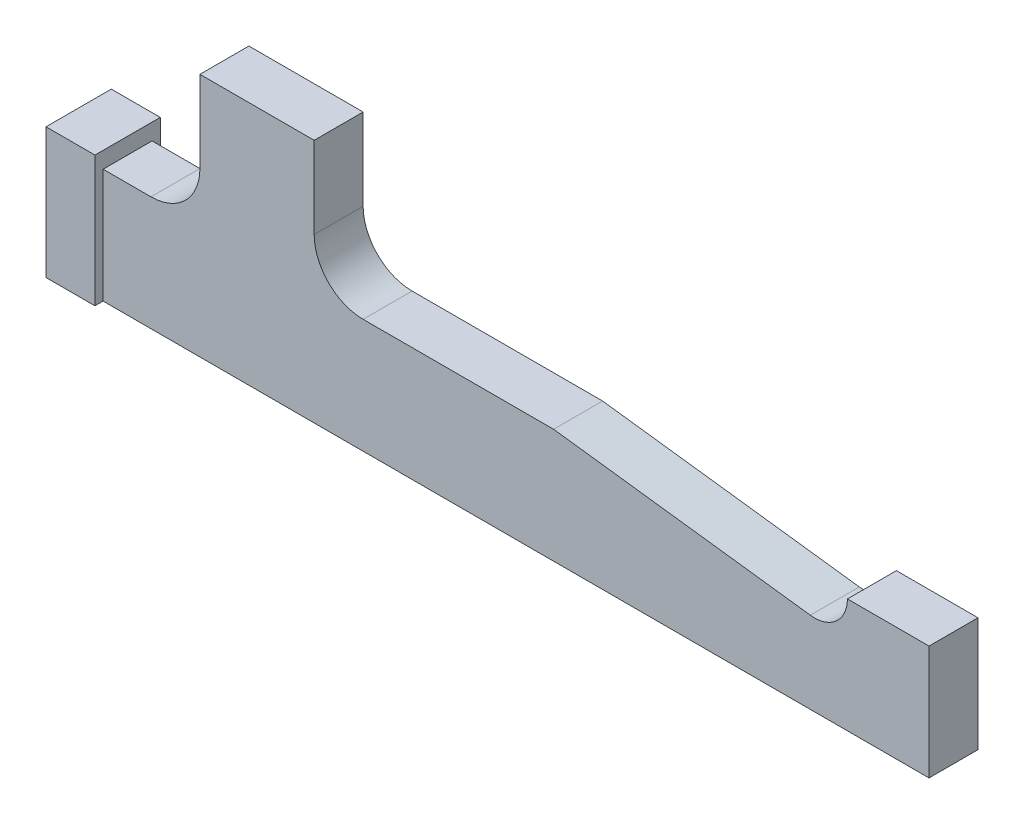
SolidWorks part; units mm, degrees
ref_plane "Front Plane" through (0, 0, 0) normal (0, 0, 1) x (1, 0, 0)
ref_plane "Top Plane" through (0, 0, 0) normal (0, 1, 0) x (1, 0, 0)
ref_plane "Right Plane" through (0, 0, 0) normal (1, 0, 0) x (0, 0, -1)
sketch "Sketch1" plane through (0, 0, 0) normal (0, 0, 1) x (1, 0, 0)
  line L0 (0, 0) -> (-50.6, 0)
  line L1 (-50.6, 7) -> (-50.6, 0)
  line L4 (0, 0) -> (0, 7)
  line L5 (0, 7) -> (-5, 7)
  line L8 (-50.6, 7) -> (-47.67, 7)
  line L9 (-44.67, 10) -> (-44.67, 15)
  line L10 (-44.67, 15) -> (-37.67, 15)
  line L11 (-37.67, 15) -> (-37.67, 10)
  line L12 (-34.67, 7) -> (-23, 7)
  line L13 (-23, 7) -> (-7.2704, 5)
  line L14 (-50.6, 7) -> (-50.6, 0)
  line L15 (0, 0) -> (0, 7)
  line L16 (-50.6, 0) -> (-53.6, 0)
  line L17 (-50.6, 0) -> (-50.6, 8)
  line L18 (-50.6, 8) -> (-53.6, 8)
  line L19 (-53.6, 0) -> (-53.6, 8)
  arc A0 (-44.67, 10) -> (-47.67, 7) centre (-47.67, 10) cw
  arc A1 (-37.67, 10) -> (-34.67, 7) centre (-34.67, 10) ccw
  arc A2 (-5, 7) -> (-7.2704, 5) centre (-7.0161, 7) cw
  dimension "D1" = 8
  dimension "D9" = 3
  dimension "D11" = 5
  dimension "D12" = 3
  dimension "D2" = 1
  dimension "D3" = 7
  dimension "D4" = 53.6
  dimension "D5" = 3
  dimension "D6" = 5
  dimension "D7" = 23
  dimension "D8" = 7
  dimension "D10" = 15
  dimension "D13" = 15.93
extrude "Boss-Extrude1" add sketch "Sketch1" along normal mid plane 3 contours L5 A2 L13 L12 A1 L11 L10 L9 A0 L8 L1 L0 L4 region at (-28.3954, 4.4676, 0)
extrude "Boss-Extrude2" add sketch "Sketch1<6>" along normal mid plane 4 contours L19 L16 L1 L17 L18 region at (-52.1, 4, 0)
sketch "Sketch1<6>" plane through (0, 0, 0) normal (0, 0, 1) x (1, 0, 0) same geometry as "Sketch1"
